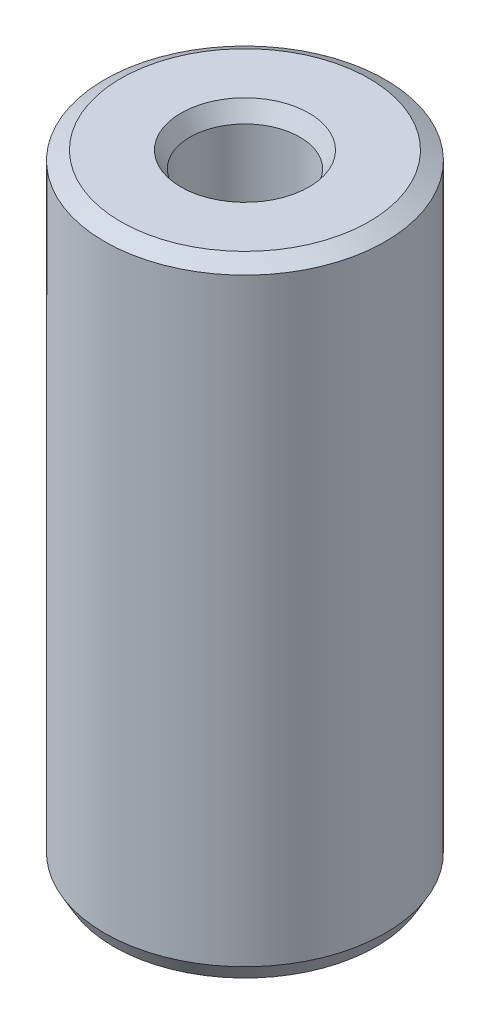
SolidWorks part; units mm, degrees
ref_plane "Front Plane" through (0, 0, 0) normal (0, 0, 1) x (1, 0, 0)
ref_plane "Top Plane" through (0, 0, 0) normal (0, 1, 0) x (1, 0, 0)
ref_plane "Right Plane" through (0, 0, 0) normal (1, 0, 0) x (0, 0, -1)
sketch "Sketch1" plane through (0, 0, 0) normal (0, 1, 0) x (1, 0, 0)
  circle A0 centre (0, 0) radius 22.5
  dimension "SLEEVE_OD" = 45
extrude "Boss-Extrude1" add sketch "Sketch1" along normal blind 100.0835
sketch "Sketch2" plane through (0, 0, 0) normal (0, 1, 0) x (1, 0, 0)
  circle A0 centre (0, 0) radius 8.8075
  dimension "BORE_D" = 17.6151
extrude "Cut-Extrude1" cut sketch "Sketch2" along normal through all
chamfer "Chamfer1" distance 1.4621 angle 60.65 4 edges at (0, 100.0835, 8.8075) (0, 0, 8.8075) (0, 0, 22.5) (0, 100.0835, 22.5) first distance on face at (0, 100.0835, 8.8075) first distance on face at (0, 0, 8.8075) first distance on face at (0, 100.0835, 22.5)
